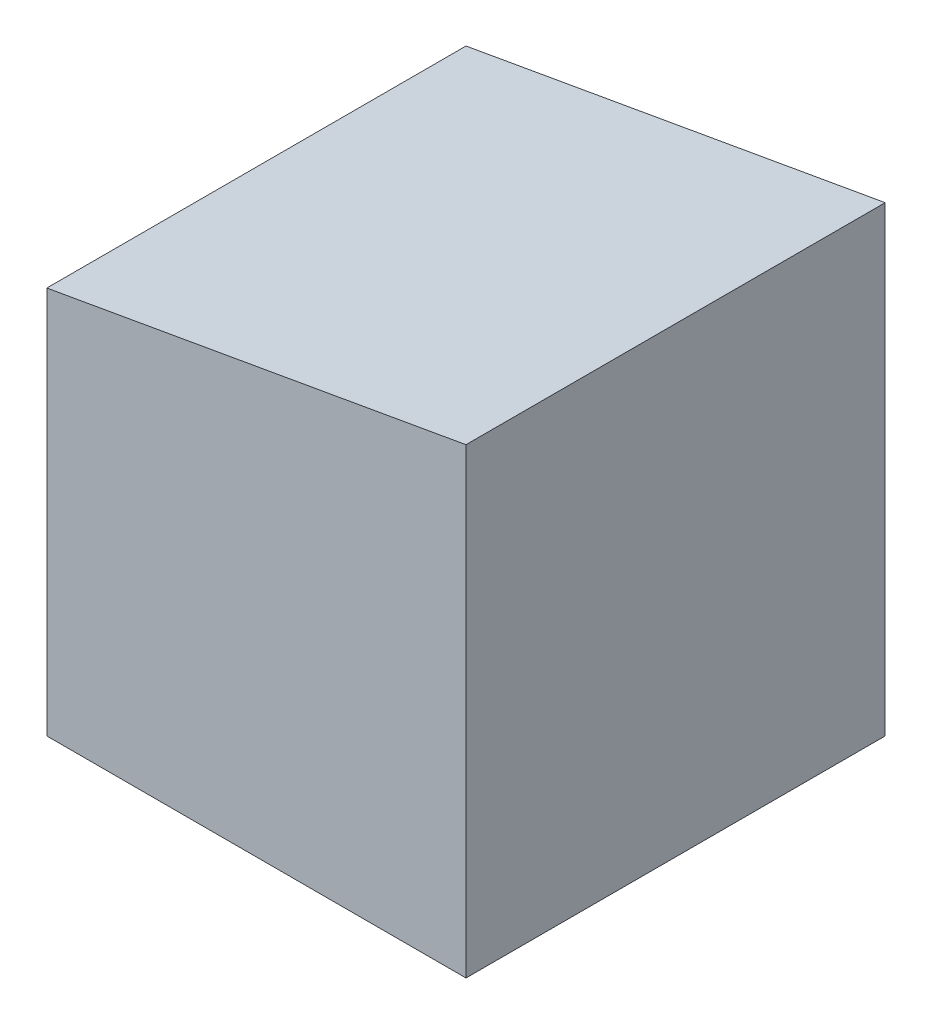
SolidWorks part; units mm, degrees
ref_plane "Front Plane" through (0, 0, 0) normal (0, 0, 1) x (1, 0, 0)
ref_plane "Top Plane" through (0, 0, 0) normal (0, 1, 0) x (1, 0, 0)
ref_plane "Right Plane" through (0, 0, 0) normal (1, 0, 0) x (0, 0, -1)
sketch "Sketch1" plane through (0, 0, 0) normal (0, 1, 0) x (1, 0, 0)
  line L1 (-44.45, -44.45) -> (44.45, -44.45)
  line L2 (-44.45, -44.45) -> (-44.45, 44.45)
  line L3 (-44.45, 44.45) -> (44.45, 44.45)
  line L4 (44.45, -44.45) -> (44.45, 44.45)
  line L5 (-44.45, -44.45) -> (44.45, 44.45) construction
  line L6 (-44.45, 44.45) -> (44.45, -44.45) construction
  point P0 (0, 0)
  dimension "D1" = 88.9
  dimension "D2" = 88.9
extrude "Boss-Extrude1" add sketch "Sketch1" along normal blind 97.95
sketch "Sketch2" plane through (0, 0, 44.45) normal (0, 0, 1) x (1, 0, 0)
  line L0 (44.45, 97.95) -> (-44.45, 82.2745)
  line L1 (-44.45, 97.95) -> (-44.45, 0) construction
  line L2 (-44.45, 82.2745) -> (-44.45, 97.95)
  line L3 (-44.45, 97.95) -> (44.45, 97.95)
  dimension "D1" = 10
extrude "Cut-Extrude1" cut sketch "Sketch2" against normal blind 135
